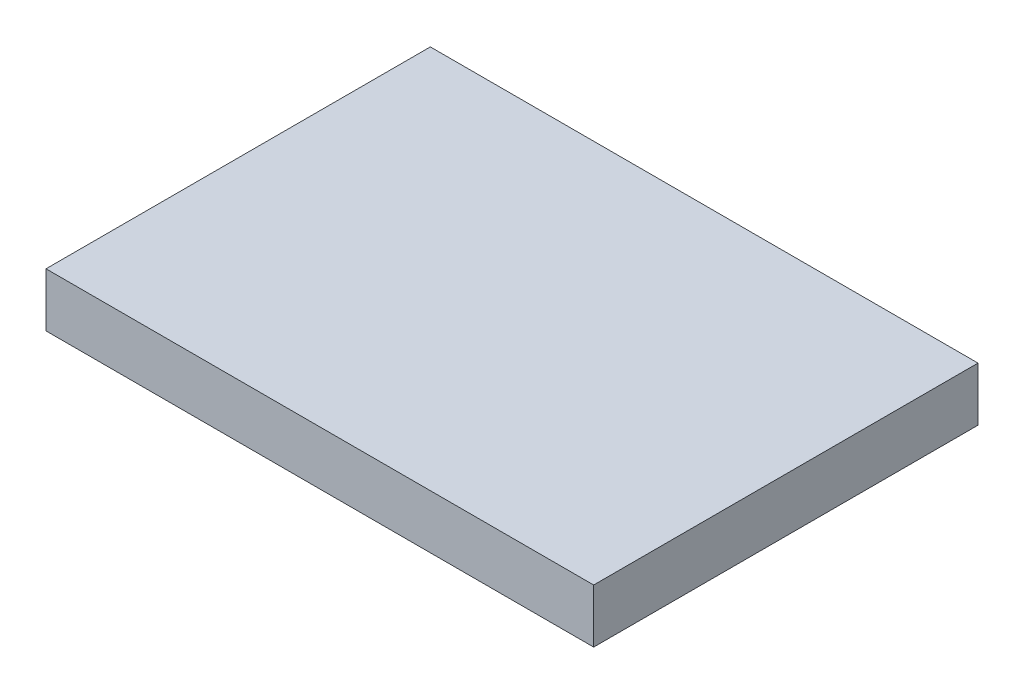
SolidWorks part; units mm, degrees
material "AISI 304"
ref_plane "Ebene vorne" through (0, 0, 0) normal (0, 0, 1) x (1, 0, 0)
ref_plane "Ebene oben" through (0, 0, 0) normal (0, 1, 0) x (1, 0, 0)
ref_plane "Ebene rechts" through (0, 0, 0) normal (1, 0, 0) x (0, 0, -1)
sketch "Skizze1" plane through (0, 0, 0) normal (1, 0, 0) x (0, 0, -1)
  line L1 (-100, -14) -> (100, -14)
  line L2 (-100, -14) -> (-100, 14)
  line L3 (-100, 14) -> (100, 14)
  line L4 (100, -14) -> (100, 14)
  line L5 (-100, -14) -> (100, 14) construction
  line L6 (-100, 14) -> (100, -14) construction
  point P0 (0, 0)
  dimension "D1" = 28
  dimension "D2" = 200
extrude "Aufsatz-Linear austragen1" add sketch "Skizze1" along normal mid plane 285
